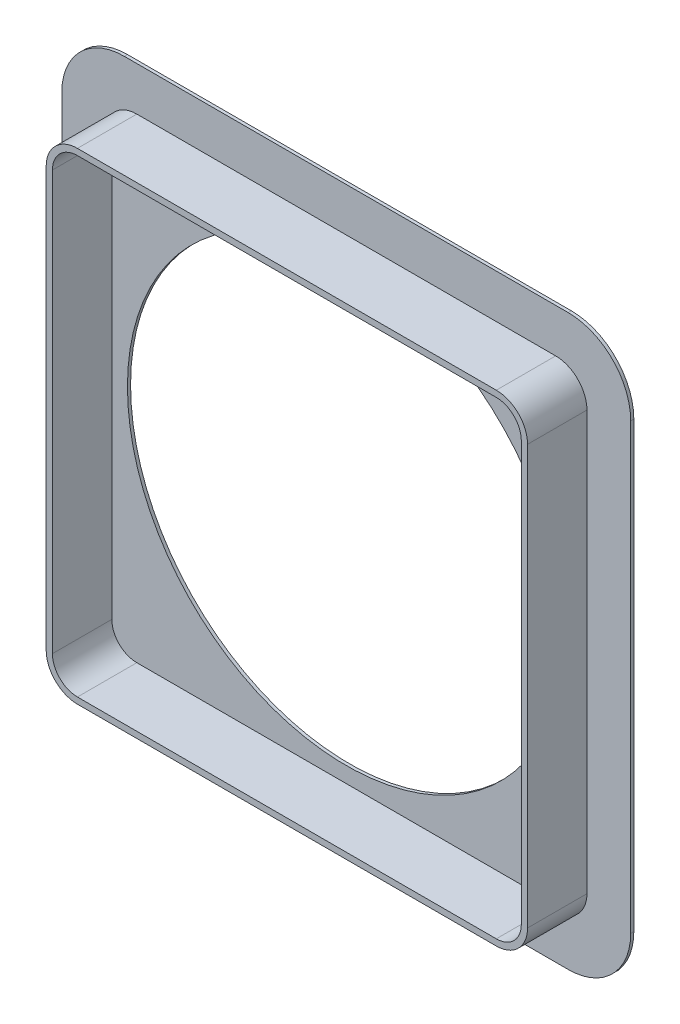
SolidWorks part; units mm, degrees
ref_plane "Front Plane" through (0, 0, 0) normal (0, 0, 1) x (1, 0, 0)
ref_plane "Top Plane" through (0, 0, 0) normal (0, 1, 0) x (1, 0, 0)
ref_plane "Right Plane" through (0, 0, 0) normal (1, 0, 0) x (0, 0, -1)
sketch "Sketch1" plane through (0, 0, 0) normal (0, 0, 1) x (1, 0, 0)
  line L1 (-45.5, -45.5) -> (45.5, -45.5)
  line L2 (-45.5, -45.5) -> (-45.5, 45.5)
  line L3 (-45.5, 45.5) -> (45.5, 45.5)
  line L4 (45.5, -45.5) -> (45.5, 45.5)
  line L5 (-45.5, -45.5) -> (45.5, 45.5) construction
  line L6 (-45.5, 45.5) -> (45.5, -45.5) construction
  point P0 (0, 0)
  dimension "D1" = 91
  dimension "D2" = 91
extrude "Boss-Extrude1" add sketch "Sketch1" along normal blind 0.5
sketch "Sketch2" plane through (0, 0, 0) normal (0, 0, 1) x (1, 0, 0)
  line L1 (-38.5, -38.5) -> (38.5, -38.5)
  line L2 (-38.5, -38.5) -> (-38.5, 38.5)
  line L3 (-38.5, 38.5) -> (38.5, 38.5)
  line L4 (38.5, -38.5) -> (38.5, 38.5)
  line L5 (-38.5, -38.5) -> (38.5, 38.5) construction
  line L6 (-38.5, 38.5) -> (38.5, -38.5) construction
  point P0 (0, 0)
  dimension "D1" = 77
  dimension "D2" = 77
extrude "Boss-Extrude2" add sketch "Sketch2" along normal blind 10
fillet "Fillet1" radius 5 4 edges at (38.5, -38.5, 5.25) (-38.5, -38.5, 5.25) (-38.5, 38.5, 5.25) (38.5, 38.5, 5.25)
sketch "Sketch6" plane through (0, 0, 0.5) normal (0, 0, 1) x (1, 0, 0)
  line L0 (-40.5, 45.5) -> (40.5, 45.5)
  line L1 (45.5, 45.5) -> (-45.5, 45.5) construction
  line L2 (45.5, -45.5) -> (45.5, 45.5) construction
  line L3 (-45.5, 45.5) -> (-45.5, -45.5) construction
  dimension "D1" = 5
  dimension "D2" = 5
extrude "Extrude-Thin1" [suppressed] add sketch "Sketch6" along normal up to surface (9.5 mm away) thin thin type one direction wall 1
sketch "Sketch4" plane through (0, 0, 10) normal (0, 0, 1) x (1, 0, 0)
  line L8 (-33.5, -37.5) -> (33.5, -37.5)
  line L9 (37.5, -33.5) -> (37.5, 33.5)
  line L10 (33.5, 37.5) -> (-33.5, 37.5)
  line L11 (-37.5, 33.5) -> (-37.5, -33.5)
  line L12 (-33.5, -37.5) -> (33.5, -37.5)
  line L13 (37.5, -33.5) -> (37.5, 33.5)
  line L14 (33.5, 37.5) -> (-33.5, 37.5)
  line L15 (-37.5, 33.5) -> (-37.5, -33.5)
  arc A8 (33.5, -37.5) -> (37.5, -33.5) centre (33.5, -33.5) ccw
  arc A9 (37.5, 33.5) -> (33.5, 37.5) centre (33.5, 33.5) ccw
  arc A10 (-33.5, 37.5) -> (-37.5, 33.5) centre (-33.5, 33.5) ccw
  arc A11 (-37.5, -33.5) -> (-33.5, -37.5) centre (-33.5, -33.5) ccw
  arc A12 (33.5, -37.5) -> (37.5, -33.5) centre (33.5, -33.5) ccw
  arc A13 (37.5, 33.5) -> (33.5, 37.5) centre (33.5, 33.5) ccw
  arc A14 (-33.5, 37.5) -> (-37.5, 33.5) centre (-33.5, 33.5) ccw
  arc A15 (-37.5, -33.5) -> (-33.5, -37.5) centre (-33.5, -33.5) ccw
  dimension "D1" = 1
extrude "Cut-Extrude1" cut sketch "Sketch4" against normal through all
ref_axis "Axis1" [suppressed] through (0, 0, -0.5) along (0, 0, 1)
pattern_circular "CirPattern1" [suppressed] count 4 over 360 about axis through (0, 0, -0.5) along (0, 0, 1) of bodies 103
fillet "Fillet2" radius 10 4 edges at (45.5, -45.5, 0.25) (-45.5, -45.5, 0.25) (-45.5, 45.5, 0.25) (45.5, 45.5, 0.25)
sketch "Sketch7" plane through (0, 0, 0) normal (0, 0, 1) x (1, 0, 0)
  line L4 (-33.5, -37.5) -> (33.5, -37.5)
  line L5 (37.5, -33.5) -> (37.5, 33.5)
  line L6 (33.5, 37.5) -> (-33.5, 37.5)
  line L7 (-37.5, 33.5) -> (-37.5, -33.5)
  line L8 (-33.5, -37.5) -> (33.5, -37.5)
  line L9 (37.5, -33.5) -> (37.5, 33.5)
  line L10 (33.5, 37.5) -> (-33.5, 37.5)
  line L11 (-37.5, 33.5) -> (-37.5, -33.5)
  circle A0 centre (0, 0) radius 35
  arc A5 (-37.5, -33.5) -> (-33.5, -37.5) centre (-33.5, -33.5) ccw
  arc A6 (33.5, -37.5) -> (37.5, -33.5) centre (33.5, -33.5) ccw
  arc A7 (37.5, 33.5) -> (33.5, 37.5) centre (33.5, 33.5) ccw
  arc A8 (-33.5, 37.5) -> (-37.5, 33.5) centre (-33.5, 33.5) ccw
  arc A9 (-37.5, -33.5) -> (-33.5, -37.5) centre (-33.5, -33.5) ccw
  arc A10 (33.5, -37.5) -> (37.5, -33.5) centre (33.5, -33.5) ccw
  arc A11 (37.5, 33.5) -> (33.5, 37.5) centre (33.5, 33.5) ccw
  arc A12 (-33.5, 37.5) -> (-37.5, 33.5) centre (-33.5, 33.5) ccw
  dimension "D2" = 70
  dimension "D1" = 0
extrude "Boss-Extrude3" add sketch "Sketch7" along normal up to surface (0.5 mm away) up to face at (0, 0, 0.5)
